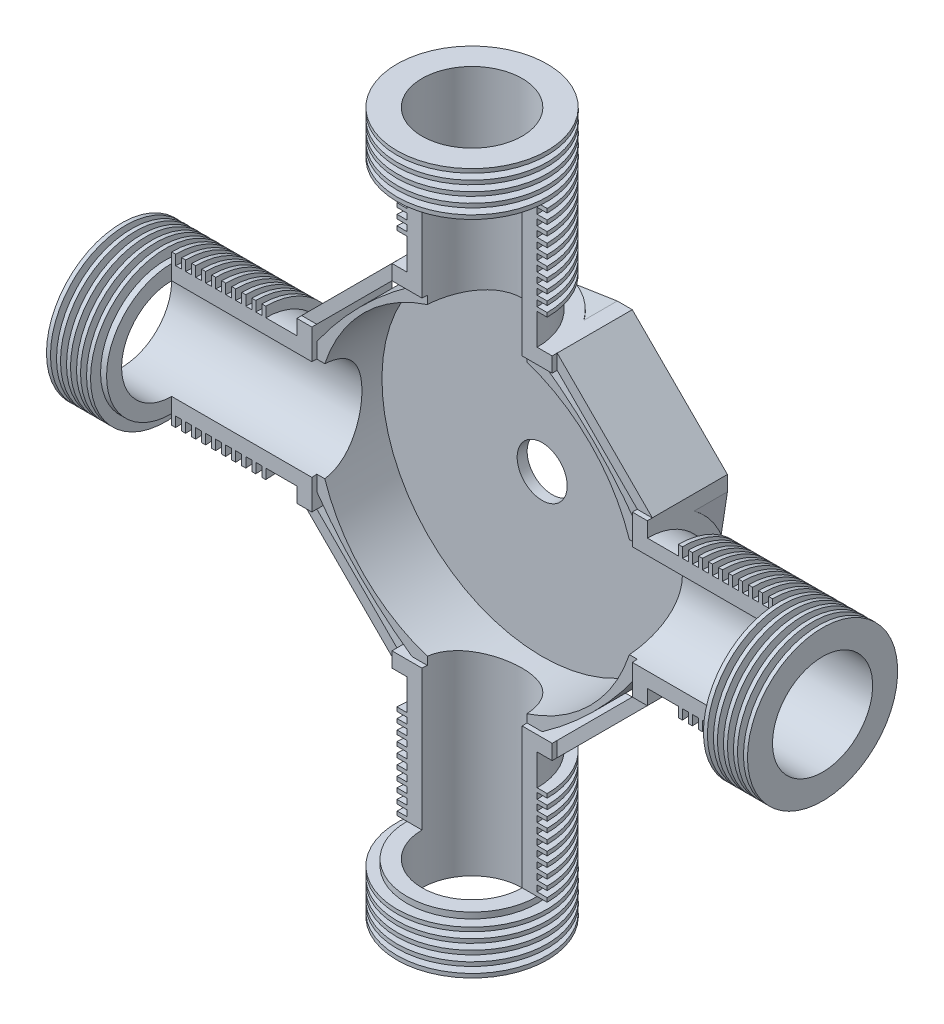
SolidWorks part; units mm, degrees
note: The reader was unsure of these and kept them because the rebuilt part matched: shared geometry of "Sketch8<9>".
material "Copper"
ref_plane "Front Plane" through (0, 0, 0) normal (0, 0, 1) x (1, 0, 0)
ref_plane "Top Plane" through (0, 0, 0) normal (0, 1, 0) x (1, 0, 0)
ref_plane "Right Plane" through (0, 0, 0) normal (1, 0, 0) x (0, 0, -1)
sketch "Sketch6" plane through (0, 0, 0) normal (0, 0, 1) x (1, 0, 0)
  circle A0 centre (0, 0) radius 160
  circle A1 centre (0, 0) radius 25
  dimension "D1" = 320
  dimension "D2" = 50
extrude "Boss-Extrude2" add sketch "Sketch6" along normal blind 10
sketch "Sketch8" plane through (0, 0, 0) normal (1, 0, 0) x (0, 0, -1)
  line L0 (-10, 160) -> (-30, 160)
  line L1 (-30, 160) -> (-30, 350)
  line L4 (-145, 300) -> (-80, 300)
  line L5 (-80, 300) -> (-80, 160)
  line L7 (-30, 350) -> (-15, 350)
  line L8 (-15, 346) -> (-15, 340)
  line L9 (-15, 175) -> (0, 175)
  line L10 (0, 385) -> (0, -385) construction
  line L11 (-10, 160) -> (0, 160)
  line L13 (-80, 300) -> (-80, 351.3474)
  line L14 (-145, 300) -> (-145, 160)
  line L15 (-145, 160) -> (-80, 160)
  line L16 (-15, 350) -> (-5, 350)
  line L17 (-5, 350) -> (-5, 346)
  line L18 (-5, 346) -> (-15, 346)
  line L19 (-5, 340) -> (-5, 336)
  line L20 (-15, 340) -> (-5, 340)
  line L21 (-5, 336) -> (-15, 336)
  line L22 (-5, 330) -> (-5, 326)
  line L23 (-15, 330) -> (-5, 330)
  line L24 (-5, 326) -> (-15, 326)
  line L25 (-5, 320) -> (-5, 316)
  line L26 (-15, 320) -> (-5, 320)
  line L27 (-5, 316) -> (-15, 316)
  line L28 (-5, 310) -> (-5, 306)
  line L29 (-15, 310) -> (-5, 310)
  line L30 (-5, 306) -> (-15, 306)
  line L31 (-5, 300) -> (-5, 296)
  line L32 (-15, 300) -> (-5, 300)
  line L33 (-5, 296) -> (-15, 296)
  line L34 (-5, 290) -> (-5, 286)
  line L35 (-15, 290) -> (-5, 290)
  line L36 (-5, 286) -> (-15, 286)
  line L37 (-5, 280) -> (-5, 276)
  line L38 (-15, 280) -> (-5, 280)
  line L39 (-5, 276) -> (-15, 276)
  line L40 (-5, 270) -> (-5, 266)
  line L41 (-15, 270) -> (-5, 270)
  line L42 (-5, 266) -> (-15, 266)
  line L43 (-5, 260) -> (-5, 256)
  line L44 (-15, 260) -> (-5, 260)
  line L45 (-5, 256) -> (-15, 256)
  line L46 (-5, 250) -> (-5, 246)
  line L47 (-15, 250) -> (-5, 250)
  line L48 (-5, 246) -> (-15, 246)
  line L49 (-5, 240) -> (-5, 236)
  line L50 (-15, 240) -> (-5, 240)
  line L51 (-5, 236) -> (-15, 236)
  line L52 (-5, 230) -> (-5, 226)
  line L53 (-15, 230) -> (-5, 230)
  line L54 (-5, 226) -> (-15, 226)
  line L55 (-5, 220) -> (-5, 216)
  line L56 (-15, 220) -> (-5, 220)
  line L57 (-5, 216) -> (-15, 216)
  line L58 (-5, 210) -> (-5, 206)
  line L59 (-15, 210) -> (-5, 210)
  line L60 (-5, 206) -> (-15, 206)
  line L62 (-15, 336) -> (-15, 330)
  line L63 (-15, 326) -> (-15, 320)
  line L64 (-15, 316) -> (-15, 310)
  line L65 (-15, 306) -> (-15, 300)
  line L66 (-15, 296) -> (-15, 290)
  line L67 (-15, 286) -> (-15, 280)
  line L68 (-15, 276) -> (-15, 270)
  line L69 (-15, 266) -> (-15, 260)
  line L70 (-15, 256) -> (-15, 250)
  line L71 (-15, 246) -> (-15, 240)
  line L72 (-15, 236) -> (-15, 230)
  line L73 (-15, 226) -> (-15, 220)
  line L74 (-15, 206) -> (-15, 175)
  line L75 (-15, 216) -> (-15, 210)
  line L76 (0, 160) -> (-10, 160) construction
  line L77 (0, 160) -> (0, 175)
  dimension "D1" = 65
  dimension "D2" = 15
  dimension "D3" = 15
  dimension "D4" = 65
  dimension "D5" = 15
  dimension "D6" = 140
  dimension "D7" = 350
  dimension "D8" = 10
  dimension "D9" = 4
  dimension "D11" = 6
  dimension "D12" = 50
  dimension "D10" = 15
revolve "Revolve5" add sketch "Sketch8" angle 360 about L5
extrude "Cut-Extrude1" cut sketch "Sketch8<9>" against normal through all and the other way through all contours L5 L15 L14 L4
sketch "Sketch8<9>" plane through (0, 0, 0) normal (1, 0, 0) x (0, 0, -1) same geometry as "Sketch8"
pattern_circular "CirPattern3" count 4 over 360 about axis through (0, 0, 0) along (0, 0, 1) of bodies 119
sketch "Sketch9" plane through (0, 0, 0) normal (0, 0, 1) x (1, 0, 0)
  line L0 (-175, 80) -> (-80, 175)
  line L1 (-80, 160) -> (-160, 80)
  line L2 (-160, 80) -> (-160, 65)
  line L3 (-160, 50) -> (-160, 80) construction
  line L4 (-160, 65) -> (-150, 65)
  line L6 (-65, 150) -> (-65, 160)
  line L7 (-80, 160) -> (-50, 160) construction
  line L8 (-65, 160) -> (-80, 160)
  line L9 (-160, 50) -> (-160, 0)
  line L10 (-160, -50) -> (-160, 50) construction
  line L11 (-50, 160) -> (0, 160)
  line L12 (0, -85.25) -> (0, 85.25) construction
  line L13 (-175, 80) -> (-160, 50)
  line L14 (-80, 175) -> (-50, 160)
  line L15 (80, 175) -> (175, 80)
  line L16 (80, 175) -> (50, 160)
  line L17 (150, 65) -> (160, 65)
  line L18 (160, 65) -> (160, 80)
  line L19 (160, 80) -> (80, 160)
  line L20 (80, 160) -> (65, 160)
  line L21 (65, 160) -> (65, 150)
  line L22 (175, 80) -> (160, 50)
  line L23 (160, 50) -> (160, 0)
  line L24 (50, 160) -> (0, 160)
  line L25 (175, -80) -> (80, -175)
  line L26 (175, -80) -> (160, -50)
  line L27 (65, -150) -> (65, -160)
  line L28 (65, -160) -> (80, -160)
  line L29 (80, -160) -> (160, -80)
  line L30 (160, -80) -> (160, -65)
  line L31 (160, -65) -> (150, -65)
  line L32 (80, -175) -> (50, -160)
  line L33 (50, -160) -> (0, -160)
  line L34 (160, -50) -> (160, 0)
  line L35 (-80, -175) -> (-175, -80)
  line L36 (-80, -175) -> (-50, -160)
  line L37 (-150, -65) -> (-160, -65)
  line L38 (-160, -65) -> (-160, -80)
  line L39 (-160, -80) -> (-80, -160)
  line L40 (-80, -160) -> (-65, -160)
  line L41 (-65, -160) -> (-65, -150)
  line L42 (-175, -80) -> (-160, -50)
  line L43 (-160, -50) -> (-160, 0)
  line L44 (-50, -160) -> (0, -160)
  arc A0 (-150, 65) -> (-65, 150) centre (19.951, -19.951) cw
  arc A3 (65, 150) -> (150, 65) centre (-19.951, -19.951) cw
  circle A4 centre (0, 0) radius 160
  circle A5 centre (0, 0) radius 160
  arc A6 (150, -65) -> (65, -150) centre (-19.951, 19.951) cw
  arc A7 (-65, -150) -> (-150, -65) centre (19.951, 19.951) cw
  point P72 (0, 0)
  dimension "D1" = 190
  dimension "D2" = 10
  dimension "D3" = 10
  dimension "D4" = 0
  dimension "D5" = 4
sketch "Sketch12" plane through (0, 0, 0) normal (0, 0, 1) x (1, 0, 0)
  line L0 (-175, 80) -> (-80, 175)
  line L1 (-80, 175) -> (-65, 175)
  line L2 (-65, 175) -> (0, 165)
  line L3 (0, -85.25) -> (0, 85.25) construction
  line L4 (-175, 80) -> (-175, 65)
  line L6 (-160, 80) -> (-80, 160)
  line L7 (-80, 160) -> (-65, 160)
  line L8 (-80, 160) -> (-50, 160) construction
  line L9 (-160, 80) -> (-160, 65)
  line L10 (-160, 50) -> (-160, 80) construction
  line L11 (-175, 65) -> (-165, 0)
  line L12 (85.25, 0) -> (-85.25, 0) construction
  line L13 (80, 175) -> (175, 80)
  line L14 (65, 175) -> (0, 165)
  line L15 (80, 175) -> (65, 175)
  line L16 (80, 160) -> (160, 80)
  line L17 (80, 160) -> (65, 160)
  line L18 (160, 80) -> (160, 65)
  line L19 (175, 80) -> (175, 65)
  line L20 (175, 65) -> (165, 0)
  line L21 (175, -80) -> (80, -175)
  line L22 (175, -65) -> (165, 0)
  line L23 (175, -80) -> (175, -65)
  line L24 (160, -80) -> (80, -160)
  line L25 (160, -80) -> (160, -65)
  line L26 (80, -160) -> (65, -160)
  line L27 (80, -175) -> (65, -175)
  line L28 (65, -175) -> (0, -165)
  line L29 (-80, -175) -> (-175, -80)
  line L30 (-65, -175) -> (0, -165)
  line L31 (-80, -175) -> (-65, -175)
  line L32 (-80, -160) -> (-160, -80)
  line L33 (-80, -160) -> (-65, -160)
  line L34 (-160, -80) -> (-160, -65)
  line L35 (-175, -80) -> (-175, -65)
  line L36 (-175, -65) -> (-165, 0)
  circle A0 centre (0, 0) radius 160
  arc A1 (-160, 65) -> (-65, 160) centre (157.7501, -157.7501) cw
  arc A2 (65, 160) -> (160, 65) centre (-157.7501, -157.7501) cw
  arc A3 (160, -65) -> (65, -160) centre (-157.7501, 157.7501) cw
  arc A4 (-65, -160) -> (-160, -65) centre (157.7501, 157.7501) cw
  point P65 (0, 0)
  dimension "D1" = 388.0498
  dimension "D4" = 320
  dimension "D2" = 165
  dimension "D3" = 165
  dimension "D5" = 4
extrude "Boss-Extrude4" add sketch "Sketch12" along normal blind 75
sketch "Sketch13" plane through (0, 0, 0) normal (0, 1, 0) x (1, 0, 0)
  line L0 (-49.7494, -75) -> (49.7494, -75)
  arc A0 (-49.7494, -75) -> (49.7494, -75) centre (0, -80) cw
  dimension "D1" = 50
extrude "Cut-Extrude2" cut sketch "Sketch13" against normal through all
pattern_circular "CirPattern4" count 4 over 360 about axis through (0, 0, 10) along (0, 0, 1) of "Cut-Extrude2"
